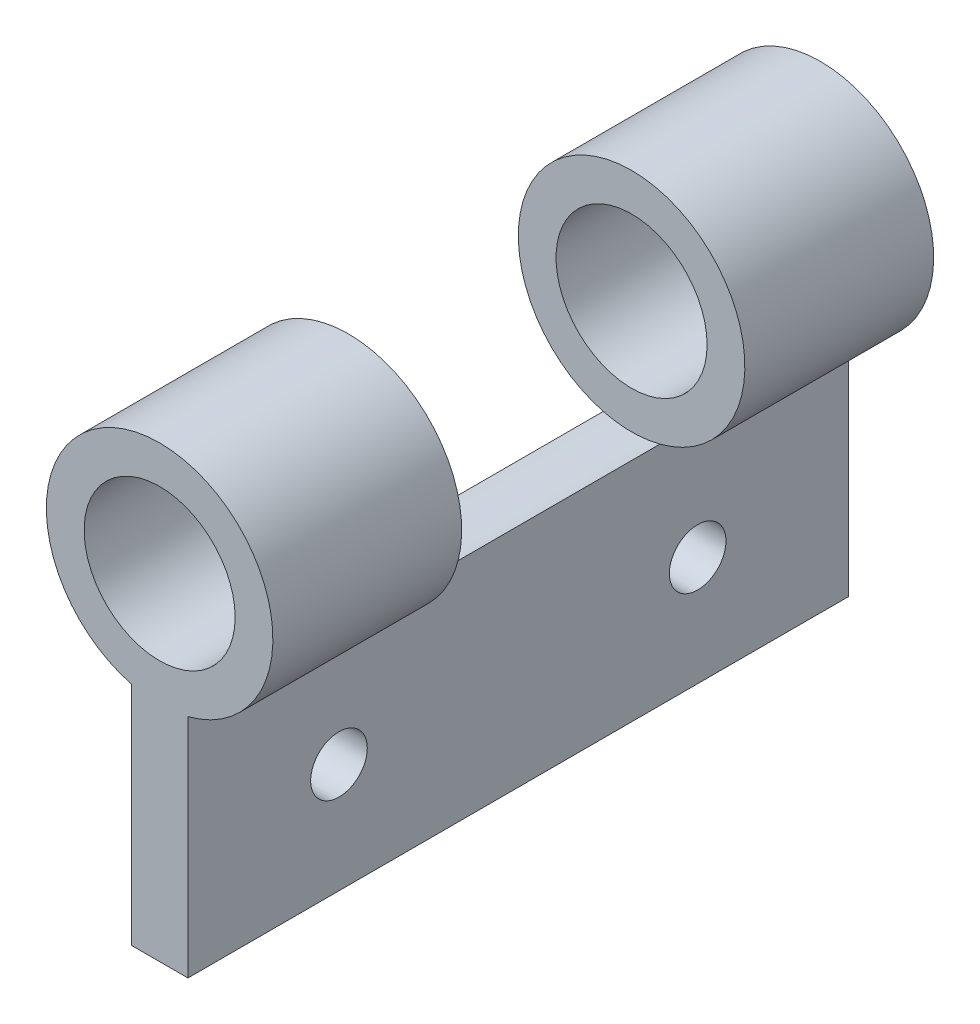
SolidWorks part; units mm, degrees
material "7075-T6, Plate (SS)"
ref_plane "Front Plane" through (0, 0, 0) normal (0, 0, 1) x (1, 0, 0)
ref_plane "Top Plane" through (0, 0, 0) normal (0, 1, 0) x (1, 0, 0)
ref_plane "Right Plane" through (0, 0, 0) normal (1, 0, 0) x (0, 0, -1)
sketch "Sketch2" plane through (0, 0, 0) normal (0, 0, 1) x (1, 0, 0)
  line L9 (-0.75, -8.9) -> (0.75, -8.9)
  line L10 (-0.75, -8.9) -> (-0.75, -2.9)
  line L11 (-0.75, -2.9) -> (0.75, -2.9)
  line L12 (0.75, -8.9) -> (0.75, -2.9)
  circle A0 centre (0, 0) radius 3
  circle A1 centre (0, 0) radius 2
  dimension "D1" = 6
  dimension "D2" = 4
  dimension "D3" = 0.75
  dimension "D4" = 1.5
  dimension "D5" = 2.9
  dimension "D6" = 6
extrude "Boss-Extrude4" add sketch "Sketch2" against normal blind 17.5 contours L9 A1 A0 | L9 A0 | A0 L9 L11 | L11 L12 L9 L10 region at (0, -5.9342, 0) region at (-1.7856, 2.3052, 0) region at (0, -2.9401, 0)
extrude "Cut-Extrude3" cut sketch "Sketch2<4>" against normal blind 7.5 from offset 5 contours L9 A1 A0 | L9 A0 region at (-1.7856, 2.3052, 0) region at (0, -2.9401, 0) offset against normal yes
sketch "Sketch2<4>" plane through (0, 0, 0) normal (0, 0, 1) x (1, 0, 0) same geometry as "Sketch2"
sketch "Sketch4" plane through (0.75, 0, 0) normal (1, 0, 0) x (0, 0, -1)
  line L0 (0, -8.9) -> (0, -2.9047) construction
  line L1 (17.5, -8.9) -> (0, -8.9) construction
  line L2 (17.5, -8.9) -> (17.5, -2.9047) construction
  circle A0 centre (4, -6) radius 0.75
  circle A1 centre (13.5, -6) radius 0.75
  dimension "D1" = 1.5
  dimension "D2" = 4
  dimension "D3" = 2.9
  dimension "D4" = 4
  dimension "D5" = 2.9
extrude "Cut-Extrude6" cut sketch "Sketch4" against normal blind 10
